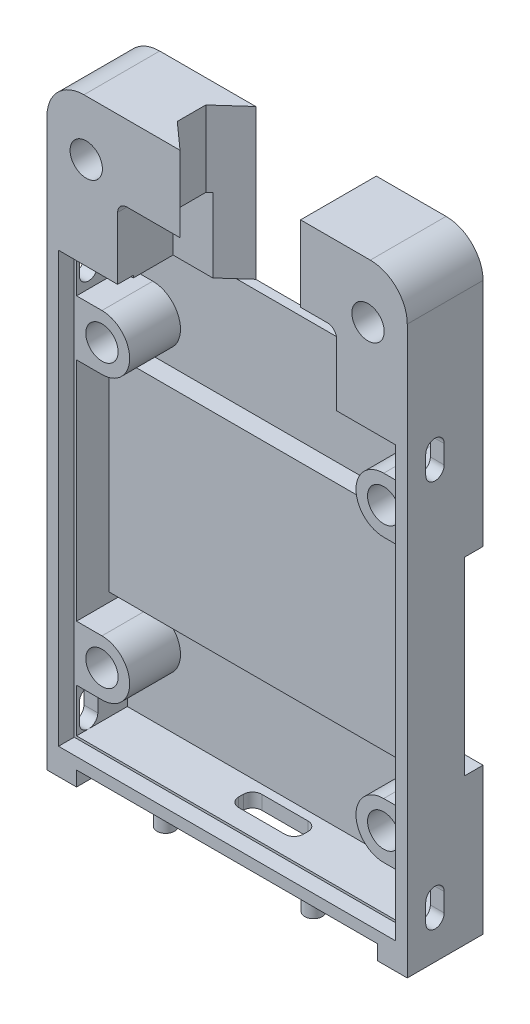
SolidWorks part; units mm, degrees
ref_plane "Front Plane" through (0, 0, 0) normal (0, 0, 1) x (1, 0, 0)
ref_plane "Top Plane" through (0, 0, 0) normal (0, 1, 0) x (1, 0, 0)
ref_plane "Right Plane" through (0, 0, 0) normal (1, 0, 0) x (0, 0, -1)
sketch "Sketch1" plane through (0, 0, 0) normal (0, 0, 1) x (1, 0, 0)
  line L0 (15.25, -20.35) -> (18, -20.35)
  line L1 (-19.5, -32.6) -> (19.5, -32.6)
  line L2 (-19.5, -32.6) -> (-19.5, 31.1)
  line L3 (-19.5, 31.1) -> (19.5, 31.1)
  line L4 (19.5, -32.6) -> (19.5, 31.1)
  line L5 (-15.25, -20.35) -> (-18, -20.35)
  line L6 (15.25, -26.35) -> (18, -26.35)
  line L7 (15.5, 31.1) -> (-15.5, 31.1) construction
  line L8 (-18, -31.1) -> (-18, 29.6)
  line L9 (-18, 29.6) -> (18, 29.6)
  line L10 (18, -31.1) -> (18, 29.6)
  line L11 (-18, -31.1) -> (18, -31.1)
  line L12 (-18, 14.9) -> (18, 14.9)
  line L13 (7.85, 14.9) -> (-4.95, 14.9) construction
  line L14 (-15.25, 4.15) -> (-18, 4.15)
  line L15 (-15.25, 10.15) -> (-18, 10.15)
  line L16 (15.25, 10.15) -> (18, 10.15)
  line L17 (15.25, 4.15) -> (18, 4.15)
  line L18 (-15.25, -26.35) -> (-18, -26.35)
  line L19 (19.5, -34.2) -> (19.5, -18.35) construction
  line L20 (-19.5, -34.2) -> (-19.5, -18.35) construction
  line L21 (15.3, -32.6) -> (-15.3, -32.6) construction
  arc A0 (19.5, 27.1) -> (15.5, 31.1) centre (15.5, 27.1) ccw construction
  arc A1 (-15.5, 31.1) -> (-19.5, 27.1) centre (-15.5, 27.1) ccw construction
  arc A2 (19.5, 27.1) -> (15.5, 31.1) centre (15.5, 27.1) ccw
  arc A3 (-15.5, 31.1) -> (-19.5, 27.1) centre (-15.5, 27.1) ccw
  arc A4 (-15.5, 29.6) -> (-18, 27.1) centre (-15.5, 27.1) ccw
  arc A5 (18, 27.1) -> (15.5, 29.6) centre (15.5, 27.1) ccw
  circle A6 centre (-15.25, -23.35) radius 1.75
  circle A7 centre (15.25, -23.35) radius 1.75
  circle A8 centre (-15.25, 7.15) radius 1.75
  circle A9 centre (15.25, 7.15) radius 1.75
  circle A10 centre (15.25, 25.15) radius 1.75
  circle A11 centre (-15.25, 25.15) radius 1.75
  circle A12 centre (-15.25, -23.35) radius 3
  circle A13 centre (15.25, -23.35) radius 3
  circle A14 centre (15.25, 7.15) radius 3
  circle A15 centre (-15.25, 7.15) radius 3
  dimension "D2" = 1.5
  dimension "D4" = 6
  dimension "D3" = 3.5
  dimension "D1" = 1.5
extrude "Base shape" add sketch "Sketch1" along normal up to surface (8.2 mm away) contours L10 A5 L9 A4 L8 L12 A11 A10 | L3 A3 L2 L1 L4 A2 A15 L8 L9 L10 A14 A13 L11 A12 | A4 L9 L8 | A5 L10 L9 | A15 L15 L8 | A15 L8 A8 | A15 L8 L14 | L8 A15 | A14 L17 L10 | L10 A14 A9 | L10 A14 | A14 L10 L16 | A13 L6 L10 | L10 A13 A7 | L10 A13 | A13 L10 L0 | A12 L8 L18 | A12 L8 A6 | L8 A12 | A12 L5 L8 region at (16.8481, -20.9099, 0) region at (17.3601, -20.8437, 0) region at (17.3601, -25.8563, 0) region at (18.1004, -23.35, 0) region at (17.3601, 4.6437, 0) region at (16.8481, 4.7099, 0) region at (18.1004, 7.15, 0) region at (17.3601, 9.6563, 0) region at (-17.3601, -25.8563, 0) region at (0, 22.1041, 0) region at (-18.1004, -23.35, 0) region at (-17.9169, -23.35, 0) region at (17.4416, 29.0416, 0) region at (-17.3601, -20.8437, 0) region at (-17.3601, 9.6563, 0) region at (-17.4416, 29.0416, 0) region at (-16.8481, 9.5901, 0) region at (-18.1004, 7.15, 0) region at (-17.3601, 4.6437, 0) region at (-18.7531, -2.75, 0)
sketch "Sketch3" plane through (19.5, 0, 0) normal (1, 0, 0) x (0, 0, -1)
  line L1 (0, -18.35) -> (-2, -18.35)
  line L2 (0, -18.35) -> (0, 2.15)
  line L3 (0, 2.15) -> (-2, 2.15)
  line L4 (-2, -18.35) -> (-2, 2.15)
  line L5 (0, -18.35) -> (2, -18.35) construction
  line L6 (0, 2.15) -> (2, 2.15) construction
  line L7 (0, -32.6) -> (0, 27.1) construction
  dimension "D1" = 2
extrude "Strap cut" cut sketch "Sketch3" against normal through all
sketch "Sketch4" plane through (0, 31.1, 0) normal (0, 1, 0) x (1, 0, 0)
  line L2 (7.95, 0) -> (-5.0998, 0)
  line L4 (-15.5, 0) -> (15.5, 0) construction
  line L5 (-15.5, -8.2) -> (15.5, -8.2) construction
  line L6 (7.95, -8.2) -> (-5.0998, -8.2)
  line L12 (7.95, -8.3) -> (7.95, 0.1)
  line L13 (7.95, 0.1) -> (-4.9883, 0.1)
  line L14 (-4.9883, 0.1) -> (-7.95, -2.5553)
  line L15 (-7.95, -2.5553) -> (-7.95, -5.6447)
  line L16 (-7.95, -5.6447) -> (-4.9883, -8.3)
  line L17 (-4.9883, -8.3) -> (7.95, -8.3)
  line L18 (7.95, -8.3) -> (7.95, 0.1)
  line L19 (7.95, 0.1) -> (-4.9883, 0.1)
  line L20 (-4.9883, 0.1) -> (-7.95, -2.5553)
  line L21 (-7.95, -2.5553) -> (-7.95, -5.6447)
  line L22 (-7.95, -5.6447) -> (-4.9883, -8.3)
  line L23 (-4.9883, -8.3) -> (7.95, -8.3)
  dimension "D1" = 0.1
extrude "XT60 cut" cut sketch "Sketch4" against normal up to next contours L21 L22 L18 L20 region at (0.4142, 31.1, 4.1)
sketch "Sketch5" plane through (19.5, 0, 0) normal (1, 0, 0) x (0, 0, -1)
  line L1 (-8.2, -32.6) -> (-8.2, 27.1) construction
  line L2 (-6.2, -31.1) -> (-4.2, -31.1)
  line L3 (-6.2, -31.1) -> (-6.2, -27.1)
  line L4 (-6.2, -27.1) -> (-4.2, -27.1)
  line L5 (-4.2, -31.1) -> (-4.2, -27.1)
  line L6 (-8.2, -31.1) -> (0, -31.1) construction
  line L7 (-8.2, 14.9) -> (0, 14.9) construction
  line L8 (-6.2, 14.9) -> (-4.2, 14.9)
  line L9 (-6.2, 14.9) -> (-6.2, 10.9)
  line L10 (-6.2, 10.9) -> (-4.2, 10.9)
  line L11 (-4.2, 14.9) -> (-4.2, 10.9)
  line L14 (-5.2, -27.1) -> (-5.2, -31.1) construction
  line L15 (-5.2, 14.9) -> (-5.2, 10.9) construction
  circle A0 centre (-5.2, -28.1) radius 1
  circle A1 centre (-5.2, -30.1) radius 1
  circle A2 centre (-5.2, 13.9) radius 1
  circle A3 centre (-5.2, 11.9) radius 1
  point P20 (-5.2, -29.1)
  point P31 (-5.2, 12.9)
  dimension "D3" = 4
  dimension "D1" = 2
  dimension "D2" = 2
extrude "Power wires cut" cut sketch "Sketch5" against normal through all contours A2 | A3 | A3 A2 L9 | A3 L11 A2 | A1 | A0 | A1 L5 A0 | A1 A0 L3 region at (19.5, -30.1, 5.2) region at (19.5, -29.1, 5.9766) region at (19.5, -29.1, 4.4234) region at (19.5, -28.1, 5.2) region at (19.5, 13.9, 5.2) region at (19.5, 12.9, 5.9766) region at (19.5, 12.9, 4.4234) region at (19.5, 11.9, 5.2)
sketch "Sketch6" plane through (0, 0, 8.2) normal (0, 0, 1) x (1, 0, 0)
  line L0 (-7.85, 15.9) -> (-7.85, 21.9) construction
  line L1 (-8.85, 22.9) -> (-10.85, 22.9) construction
  line L2 (-11.85, 15.9) -> (-11.85, 21.9) construction
  line L3 (-8.85, 14.9) -> (-10.85, 14.9) construction
  line L4 (-7.85, 15.9) -> (-7.85, 21.9)
  line L5 (-8.85, 22.9) -> (-10.85, 22.9)
  line L6 (-11.85, 15.9) -> (-11.85, 21.9)
  line L7 (-8.85, 14.9) -> (-10.85, 14.9)
  line L8 (7.85, 15.9) -> (7.85, 21.9) construction
  line L9 (8.85, 22.9) -> (10.85, 22.9) construction
  line L10 (11.85, 15.9) -> (11.85, 21.9) construction
  line L11 (8.85, 14.9) -> (10.85, 14.9) construction
  line L12 (7.85, 15.9) -> (7.85, 21.9)
  line L13 (8.85, 22.9) -> (10.85, 22.9)
  line L14 (11.85, 15.9) -> (11.85, 21.9)
  line L15 (8.85, 14.9) -> (10.85, 14.9)
  line L17 (-11.85, 15.9) -> (-7.85, 15.9)
  line L18 (-11.85, 15.9) -> (-11.85, 14.9)
  line L19 (-11.85, 14.9) -> (-7.85, 14.9)
  line L20 (-7.85, 15.9) -> (-7.85, 14.9)
  line L22 (11.85, 15.9) -> (7.85, 15.9)
  line L23 (11.85, 15.9) -> (11.85, 14.9)
  line L24 (11.85, 14.9) -> (7.85, 14.9)
  line L25 (7.85, 15.9) -> (7.85, 14.9)
  line L26 (-18, 14.9) -> (-5.0998, 14.9) construction
  line L27 (11.85, 21.9) -> (7.85, 21.9)
  line L28 (11.85, 21.9) -> (11.85, 22.9)
  line L29 (11.85, 22.9) -> (7.85, 22.9)
  line L30 (7.85, 21.9) -> (7.85, 22.9)
  line L31 (-8.85, 22.9) -> (7.95, 22.9)
  line L32 (-8.85, 22.9) -> (-8.85, 14.9)
  line L33 (-8.85, 14.9) -> (7.95, 14.9)
  line L34 (7.95, 22.9) -> (7.95, 14.9)
  line L35 (7.95, 14.9) -> (18, 14.9) construction
  line L36 (7.95, 14.9) -> (7.95, 31.1) construction
  arc A0 (-8.85, 14.9) -> (-7.85, 15.9) centre (-8.85, 15.9) ccw construction
  arc A1 (-7.85, 21.9) -> (-8.85, 22.9) centre (-8.85, 21.9) ccw construction
  arc A2 (-10.85, 22.9) -> (-11.85, 21.9) centre (-10.85, 21.9) ccw construction
  arc A3 (-11.85, 15.9) -> (-10.85, 14.9) centre (-10.85, 15.9) ccw construction
  arc A4 (-8.85, 14.9) -> (-7.85, 15.9) centre (-8.85, 15.9) ccw
  arc A5 (-7.85, 21.9) -> (-8.85, 22.9) centre (-8.85, 21.9) ccw
  arc A6 (-10.85, 22.9) -> (-11.85, 21.9) centre (-10.85, 21.9) ccw
  arc A7 (-11.85, 15.9) -> (-10.85, 14.9) centre (-10.85, 15.9) ccw
  arc A8 (8.85, 22.9) -> (7.85, 21.9) centre (8.85, 21.9) ccw construction
  arc A9 (11.85, 21.9) -> (10.85, 22.9) centre (10.85, 21.9) ccw construction
  arc A10 (10.85, 14.9) -> (11.85, 15.9) centre (10.85, 15.9) ccw construction
  arc A11 (7.85, 15.9) -> (8.85, 14.9) centre (8.85, 15.9) ccw construction
  arc A12 (8.85, 22.9) -> (7.85, 21.9) centre (8.85, 21.9) ccw
  arc A13 (11.85, 21.9) -> (10.85, 22.9) centre (10.85, 21.9) ccw
  arc A14 (10.85, 14.9) -> (11.85, 15.9) centre (10.85, 15.9) ccw
  arc A15 (7.85, 15.9) -> (8.85, 14.9) centre (8.85, 15.9) ccw
  line M1 (7.95, 31.1) -> (7.95, 14.9)
  line M15 (-5.0998, 14.9) -> (-5.0998, 31.1)
extrude "IO wires cut" cut sketch "Sketch6" against normal blind 6 contours L33 L25 L12 L30 L31 M15 | A5 L4 L20 L31 M15 | L4 A5 L32 L17 | L5 A6 L6 L17 L32 | A7 L18 | L17 A7 L32 | L32 A4 L17 | A4 L20 | A12 L29 L30 M1 | L27 L12 L22 M1 | L22 A15 M1 | A15 L25 L24 L34 | A15 L34 | A15 A14 L22 M1 | A14 L23 | L14 L27 L22 M1 | L27 A13 L13 A12 L34 | A12 L29 M1 region at (-8.3587, 19.2964, 8.2) region at (-8.4256, 15.4756, 8.2) region at (-6.4903, 18.9365, 8.2) region at (-8.0734, 15.1234, 8.2) region at (-10.2516, 15.4213, 8.2) region at (-10.3368, 19.3662, 8.2) region at (-11.6266, 15.1234, 8.2) region at (1.3751, 18.9, 8.2) region at (7.8959, 15.2606, 8.2) region at (7.8959, 22.5394, 8.2) region at (8.1604, 15.056, 8.2) region at (7.9, 18.9, 8.2) region at (7.9098, 15.7354, 8.2) region at (8.1604, 22.744, 8.2) region at (9.8661, 15.4307, 8.2) region at (9.9, 18.9, 8.2) region at (9.8661, 22.3693, 8.2) region at (11.6266, 15.1234, 8.2)
sketch "Sketch7" plane through (-18, 0, 0) normal (1, 0, 0) x (0, 0, -1)
  line L6 (0, -18.35) -> (0, -20.35)
  line L7 (-2, -18.35) -> (0, -18.35)
  line L8 (-2, 2.15) -> (-2, -18.35)
  line L9 (0, 2.15) -> (-2, 2.15)
  line L12 (0, 3.15) -> (-3, 3.15)
  line L13 (-3, 3.15) -> (-3, -19.35)
  line L14 (-3, -19.35) -> (-1, -19.35)
  line L15 (-1, -19.35) -> (-1, -20.35)
  line L16 (-1, -20.35) -> (0, -20.35)
  line L17 (0, 3.15) -> (-1, 3.15)
  line L19 (0, -31.1) -> (-1, -31.1)
  line L22 (0, -31.1) -> (0, -20.35)
  line L23 (0, -20.35) -> (-1, -20.35)
  line L24 (-1, -31.1) -> (-1, -20.35)
  line L25 (0, 3.15) -> (0, 14.9)
  line L26 (0, 14.9) -> (-1, 14.9)
  line L27 (-1, 3.15) -> (-1, 14.9)
  line L28 (-5.2, 14.9) -> (0, 14.9) construction
  line L31 (0, -20.35) -> (0, -18.35) construction
  line L32 (0, 2.15) -> (-2, 2.15) construction
  line M48 (0, -20.35) -> (0, -18.35)
  line M49 (0, -18.35) -> (-2, -18.35)
  line M50 (-2, -18.35) -> (-2, 2.15)
  line M51 (-2, 2.15) -> (0, 2.15)
  line M52 (0, 2.15) -> (0, 4.15)
  line M53 (0, 4.15) -> (-8.2, 4.15)
  line M55 (-8.2, -20.35) -> (0, -20.35)
  dimension "D1" = 1
extrude "Bottom" add sketch "Sketch7" along normal up to surface (36 mm away) contours L27 L25 L26 M53 | L27 L12 M52 M53 | L14 L15 L12 L13 M55 M48 M49 M50 M51 M52 | L24 L19 L22 M55 region at (-18, -8.5273, 2.2091) region at (-18, -25.725, 0.5) region at (-18, 3.65, 0.5) region at (-18, 9.525, 0.5) up to face at (18, -8.1, 2.55)
sketch "Sketch9" plane through (0, 0, 0) normal (0, 0, -1) x (-1, 0, 0)
  circle A0 centre (-15.25, -23.35) radius 1.75 construction
  circle A1 centre (-15.25, 7.15) radius 1.75 construction
  circle A2 centre (15.25, 7.15) radius 1.75 construction
  circle A3 centre (15.25, -23.35) radius 1.75 construction
  circle A4 centre (-15.25, -23.35) radius 1.75
  circle A5 centre (-15.25, 7.15) radius 1.75
  circle A6 centre (15.25, 7.15) radius 1.75
  circle A7 centre (15.25, -23.35) radius 1.75
extrude "Bottom holes" cut sketch "Sketch9" against normal up to next
sketch "Sketch8" plane through (0, 0, 8.2) normal (0, 0, 1) x (1, 0, 0)
  line L0 (-6.2152, 14.9) -> (-18, 14.9) construction
  line L1 (-18.25, 15.15) -> (18.25, 15.15)
  line L2 (-18.25, 15.15) -> (-18.25, -31.35)
  line L3 (-18.25, -31.35) -> (18.25, -31.35)
  line L4 (18.25, 15.15) -> (18.25, -31.35)
  line L5 (-18, 14.9) -> (-18.25, 14.9) construction
  line L6 (-18, 14.9) -> (-18, 15.15) construction
  line L7 (18, 14.9) -> (18.25, 14.9) construction
  line L8 (-18, -31.1) -> (-18, -31.35) construction
  dimension "D1" = 0.25
extrude "PCB cut" cut sketch "Sketch8" against normal blind 1.7
sketch "Sketch11" plane through (0, -32.6, 0) normal (0, -1, 0) x (1, 0, 0)
  line L0 (19.5, 8.2) -> (19.5, 0) construction
  line L1 (-19.5, 8.2) -> (19.5, 8.2)
  line L2 (-19.5, 8.2) -> (-19.5, -1.8)
  line L3 (-19.5, -1.8) -> (19.5, -1.8)
  line L4 (19.5, 8.2) -> (19.5, -1.8)
  line L5 (-19.5, 3.2) -> (19.5, 3.2) construction
  line L6 (0, -1.8) -> (0, 8.2) construction
  line L8 (-2.5, 4.45) -> (2.5, 4.45)
  line L9 (-3.5, 3.45) -> (-3.5, 2.95)
  line L10 (-2.5, 1.95) -> (2.5, 1.95)
  line L11 (3.5, 3.45) -> (3.5, 2.95)
  line L12 (-3.5, 4.45) -> (3.5, 1.95) construction
  line L13 (-3.5, 1.95) -> (3.5, 4.45) construction
  arc A0 (2.5, 4.45) -> (3.5, 3.45) centre (2.5, 3.45) cw
  arc A1 (2.5, 1.95) -> (3.5, 2.95) centre (2.5, 2.95) ccw
  arc A2 (-3.5, 2.95) -> (-2.5, 1.95) centre (-2.5, 2.95) ccw
  arc A3 (-2.5, 4.45) -> (-3.5, 3.45) centre (-2.5, 3.45) ccw
  point P11 (0, 3.2)
  dimension "D4" = 1
  dimension "D1" = 10
  dimension "D2" = 7
  dimension "D3" = 2.5
extrude "Ledbar wires cut" cut sketch "Sketch11" against normal up to next contours L8 A3 L9 A2 L10 A1 L11 A0 region at (0, -32.6, 3.2)
sketch "Sketch13" plane through (0, -32.6, 0) normal (0, -1, 0) x (1, 0, 0)
  line L0 (-19.5, 8.2) -> (19.5, 8.2) construction
  line L1 (19.5, 0) -> (16.3, 0)
  line L2 (19.5, 0) -> (19.5, 8.2)
  line L3 (19.5, 8.2) -> (16.3, 8.2)
  line L4 (16.3, 0) -> (16.3, 8.2)
  line L5 (16.1, -1.8) -> (16.1, 8.2) construction
  line L6 (0, 8.2) -> (0, 0) construction
  line L7 (-19.5, 0) -> (-16.3, 0)
  line L8 (-19.5, 0) -> (-19.5, 8.2)
  line L9 (-19.5, 8.2) -> (-16.3, 8.2)
  line L10 (-16.3, 0) -> (-16.3, 8.2)
  dimension "D1" = 0.2
extrude "Ledbar sides" add sketch "Sketch13" along normal blind 1.6
sketch "Sketch14" plane through (0, -32.6, 0) normal (0, -1, 0) x (1, 0, 0)
  circle A0 centre (8, 6.85) radius 0.95
  circle A1 centre (-8, 6.85) radius 0.95
  dimension "D1" = 1.9
extrude "Ledbar mounts" add sketch "Sketch14" along normal blind 1.8
sketch "Sketch10" [suppressed] plane through (0, 0, 2) normal (0, 0, -1) x (-1, 0, 0)
  line L0 (0, 2.15) -> (0, -18.35) construction
  line L1 (19.5, 2.15) -> (-19.5, 2.15) construction
  line L2 (19.5, -18.35) -> (-19.5, -18.35) construction
  line L3 (19.5, 2.15) -> (19.5, -18.35) construction
  line L4 (-19.5, 1.15) -> (19.5, 1.15)
  line L5 (-19.5, 1.15) -> (-19.5, 0.65)
  line L6 (-19.5, 0.65) -> (19.5, 0.65)
  line L7 (19.5, 1.15) -> (19.5, 0.65)
  line L8 (-19.5, 1.15) -> (19.5, 0.65) construction
  line L9 (-19.5, 0.65) -> (19.5, 1.15) construction
  line L10 (-19.5, 2.15) -> (19.5, 2.15) construction
  line L11 (-19.5, -1.35) -> (19.5, -1.35)
  line L12 (19.5, -0.85) -> (19.5, -1.35)
  line L13 (-19.5, -0.85) -> (19.5, -0.85)
  line L14 (-19.5, -0.85) -> (-19.5, -1.35)
  line L15 (-19.5, -3.35) -> (19.5, -3.35)
  line L16 (19.5, -2.85) -> (19.5, -3.35)
  line L17 (-19.5, -2.85) -> (19.5, -2.85)
  line L18 (-19.5, -2.85) -> (-19.5, -3.35)
  line L19 (-19.5, -5.35) -> (19.5, -5.35)
  line L20 (19.5, -4.85) -> (19.5, -5.35)
  line L21 (-19.5, -4.85) -> (19.5, -4.85)
  line L22 (-19.5, -4.85) -> (-19.5, -5.35)
  line L23 (-19.5, -7.35) -> (19.5, -7.35)
  line L24 (19.5, -6.85) -> (19.5, -7.35)
  line L25 (-19.5, -6.85) -> (19.5, -6.85)
  line L26 (-19.5, -6.85) -> (-19.5, -7.35)
  line L27 (-19.5, -9.35) -> (19.5, -9.35)
  line L28 (19.5, -8.85) -> (19.5, -9.35)
  line L29 (-19.5, -8.85) -> (19.5, -8.85)
  line L30 (-19.5, -8.85) -> (-19.5, -9.35)
  line L31 (-19.5, -11.35) -> (19.5, -11.35)
  line L32 (19.5, -10.85) -> (19.5, -11.35)
  line L33 (-19.5, -10.85) -> (19.5, -10.85)
  line L34 (-19.5, -10.85) -> (-19.5, -11.35)
  line L35 (-19.5, -13.35) -> (19.5, -13.35)
  line L36 (19.5, -12.85) -> (19.5, -13.35)
  line L37 (-19.5, -12.85) -> (19.5, -12.85)
  line L38 (-19.5, -12.85) -> (-19.5, -13.35)
  line L39 (-19.5, -15.35) -> (19.5, -15.35)
  line L40 (19.5, -14.85) -> (19.5, -15.35)
  line L41 (-19.5, -14.85) -> (19.5, -14.85)
  line L42 (-19.5, -14.85) -> (-19.5, -15.35)
  line L43 (-19.5, -17.35) -> (19.5, -17.35)
  line L44 (19.5, -16.85) -> (19.5, -17.35)
  line L45 (-19.5, -16.85) -> (19.5, -16.85)
  line L46 (-19.5, -16.85) -> (-19.5, -17.35)
  point P6 (0, 0.9)
  dimension "D1" = 1
  dimension "D2" = 0.5
  dimension "D4" = 2
  dimension "D3" = 10
extrude "3D print ribs" [suppressed] add sketch "Sketch10" along normal up to surface (2 mm away) up to face at (13.5, 7.15, 0)
sketch "Sketch15" [suppressed] plane through (0, 0, 0) normal (0, 0, -1) x (-1, 0, 0)
  line L0 (-8, -34.4) -> (-8, -32.6) construction
  line L1 (-8.95, -34.4) -> (-7.05, -34.4) construction
  line L2 (-8.95, -32.6) -> (-7.05, -32.6) construction
  line L3 (0, -32.6) -> (0, 14.9) construction
  line L4 (-8.25, -34.4) -> (-7.75, -34.4)
  line L5 (-8.25, -34.4) -> (-8.25, -32.6)
  line L6 (-8.25, -32.6) -> (-7.75, -32.6)
  line L7 (-7.75, -34.4) -> (-7.75, -32.6)
  line L8 (-8.25, -34.4) -> (-7.75, -32.6) construction
  line L9 (-8.25, -32.6) -> (-7.75, -34.4) construction
  line L10 (16.3, -32.6) -> (-16.3, -32.6) construction
  line L11 (-7.95, 14.9) -> (5.0998, 14.9) construction
  line L12 (8.25, -32.6) -> (7.75, -32.6)
  line L13 (7.75, -34.4) -> (7.75, -32.6)
  line L14 (8.25, -34.4) -> (7.75, -34.4)
  line L15 (8.25, -34.4) -> (8.25, -32.6)
  point P6 (-8, -33.5)
  dimension "D1" = 0.5
extrude "Boss-Extrude1" [suppressed] add sketch "Sketch15" against normal up to next
